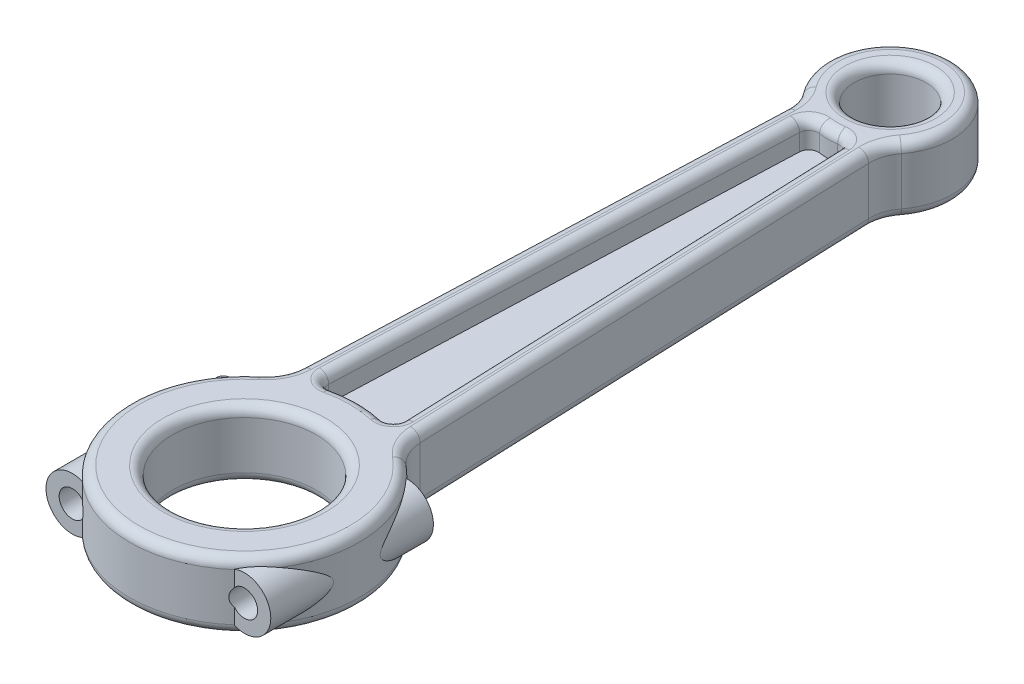
SolidWorks part; units mm, degrees
ref_plane "Alzado" through (0, 0, 0) normal (0, 0, 1) x (1, 0, 0)
ref_plane "Planta" through (0, 0, 0) normal (0, 1, 0) x (1, 0, 0)
ref_plane "Vista lateral" through (0, 0, 0) normal (1, 0, 0) x (0, 0, -1)
sketch "Croquis1" plane through (0, 0, 0) normal (0, 1, 0) x (1, 0, 0)
  line L0 (-12.5, 20.4878) -> (12.5, 20.4878) construction
  line L1 (8.5, 125.1638) -> (-8.5, 125.1638) construction
  line L2 (0, 0) -> (0, 135) construction
  line L3 (-8.6263, 121.8586) -> (-12.3507, 24.3944)
  line L4 (8.6263, 121.8586) -> (12.3507, 24.3944)
  line L5 (-4.1296, 121.6868) -> (-7.854, 24.2226) construction
  line L6 (-4.185, 120.2366) -> (-7.8083, 25.419)
  line L7 (4.185, 120.2366) -> (7.8083, 25.419)
  line L8 (4.1296, 121.6868) -> (7.854, 24.2226) construction
  arc A0 (-15.2587, 18.5249) -> (15.2587, 18.5249) centre (0, 0) ccw
  arc A1 (10.2889, 127.054) -> (-10.2889, 127.054) centre (0, 135) ccw
  arc A2 (-4.185, 120.2366) -> (-1.8949, 122.1388) centre (-2.1865, 120.1602) cw
  arc A3 (15.2587, 18.5249) -> (12.3507, 24.3944) centre (20.3449, 24.6999) cw
  arc A4 (-15.2587, 18.5249) -> (-12.3507, 24.3944) centre (-20.3449, 24.6999) ccw
  arc A5 (10.2889, 127.054) -> (8.6263, 121.8586) centre (16.6205, 122.1641) ccw
  arc A6 (-8.6263, 121.8586) -> (-10.2889, 127.054) centre (-16.6205, 122.1641) ccw
  arc A7 (-1.8949, 122.1388) -> (1.8949, 122.1388) centre (0, 135) ccw
  arc A8 (-15.2587, 18.5249) -> (15.2587, 18.5249) centre (0, 0) ccw
  circle A9 centre (0, 135) radius 7.5
  arc A11 (5.3628, 23.3932) -> (-5.3628, 23.3932) centre (0, 0) ccw
  arc A13 (-4.1296, 121.6868) -> (-6.7273, 129.8045) centre (-16.6205, 122.1641) ccw construction
  arc A15 (6.7273, 129.8045) -> (4.1296, 121.6868) centre (16.6205, 122.1641) ccw construction
  arc A16 (6.7273, 129.8045) -> (-6.7273, 129.8045) centre (0, 135) ccw construction
  arc A17 (10.2889, 127.054) -> (-10.2889, 127.054) centre (0, 135) ccw
  arc A18 (-12.3977, 15.0515) -> (12.3977, 15.0515) centre (0, 0) ccw construction
  arc A19 (-12.3977, 15.0515) -> (-7.854, 24.2226) centre (-20.3449, 24.6999) ccw construction
  arc A20 (12.3977, 15.0515) -> (7.854, 24.2226) centre (20.3449, 24.6999) cw construction
  arc A21 (1.8949, 122.1388) -> (4.185, 120.2366) centre (2.1865, 120.1602) cw
  arc A22 (5.3628, 23.3932) -> (7.8083, 25.419) centre (5.8097, 25.3426) ccw
  arc A23 (-5.3628, 23.3932) -> (-7.8083, 25.419) centre (-5.8097, 25.3426) cw
  dimension "D2" = 24
  dimension "D4" = 13
  dimension "D6" = 8
  dimension "D7" = 2
  dimension "D9" = 15
  dimension "D1" = 25
  dimension "D3" = 17
  dimension "D5" = 135
  dimension "D8" = 4.5
extrude "Saliente-Extruir2" add sketch "Croquis1" along normal mid plane 14 contours A6 L3 A4 A0 A3 L4 A5 A1 A9 A11 A23 L6 A2 A7 A21 L7 A22 region at (-7.3003, 0, -125.1466)
sketch "Croquis2" plane through (0, 0, 0) normal (0, 1, 0) x (1, 0, 0)
  line L0 (-4.185, 120.2366) -> (-7.8083, 25.419) construction
  line L1 (4.185, 120.2366) -> (7.8083, 25.419) construction
  line L2 (-4.185, 120.2366) -> (-7.8083, 25.419)
  line L3 (4.185, 120.2366) -> (7.8083, 25.419)
  arc A0 (-1.8949, 122.1388) -> (-4.185, 120.2366) centre (-2.1865, 120.1602) ccw construction
  arc A1 (-1.8949, 122.1388) -> (1.8949, 122.1388) centre (0, 135) ccw construction
  arc A2 (4.185, 120.2366) -> (1.8949, 122.1388) centre (2.1865, 120.1602) ccw construction
  arc A3 (-7.8083, 25.419) -> (-5.3628, 23.3932) centre (-5.8097, 25.3426) ccw construction
  arc A4 (5.3628, 23.3932) -> (-5.3628, 23.3932) centre (0, 0) ccw construction
  arc A5 (5.3628, 23.3932) -> (7.8083, 25.419) centre (5.8097, 25.3426) ccw construction
  arc A6 (-1.8949, 122.1388) -> (-4.185, 120.2366) centre (-2.1865, 120.1602) ccw
  arc A7 (-1.8949, 122.1388) -> (1.8949, 122.1388) centre (0, 135) ccw
  arc A8 (4.185, 120.2366) -> (1.8949, 122.1388) centre (2.1865, 120.1602) ccw
  arc A9 (-7.8083, 25.419) -> (-5.3628, 23.3932) centre (-5.8097, 25.3426) ccw
  arc A10 (5.3628, 23.3932) -> (-5.3628, 23.3932) centre (0, 0) ccw
  arc A11 (5.3628, 23.3932) -> (7.8083, 25.419) centre (5.8097, 25.3426) ccw
extrude "Saliente-Extruir3" add sketch "Croquis2" along normal mid plane 3
sketch "Croquis3" plane through (0, 0, 0) normal (0, 0, 1) x (1, 0, 0)
  line L0 (-18, 0) -> (18, 0) construction
  circle A0 centre (-18, 0) radius 5.5
  circle A1 centre (18, 0) radius 5.5
  dimension "D2" = 11
  dimension "D1" = 36
extrude "Saliente-Extruir6" add sketch "Croquis3" along normal blind 18 and the other way blind 16 contours A1 | A0
sketch "Croquis6" plane through (0, 0, 0) normal (0, 0, 1) x (1, 0, 0)
  line L0 (-18, 0) -> (18, 0) construction
  circle A0 centre (-18, 0) radius 2.75
  circle A1 centre (18, 0) radius 2.75
  dimension "D2" = 5.5
  dimension "D1" = 36
extrude "Cortar-Extruir4" cut sketch "Croquis6" against normal mid plane 48
sketch "Croquis7" plane through (0, 7, 0) normal (0, 1, 0) x (1, 0, 0)
  circle A0 centre (0, 0) radius 15
  dimension "D1" = 30
extrude "Cortar-Extruir5" cut sketch "Croquis7" against normal up to next
fillet "Redondeo1" radius 2 36 edges at (0, -7, -24) (-7.0856, -7, -23.8024) (-5.9966, -7, -72.8278) (-3.4644, -7, -121.6987) (0, -7, -122) (3.4644, -7, -121.6987) (5.9966, -7, -72.8278) (-10.4885, 7, -73.1265) (-13.1764, 7, -21.1484) (0, 7, 24) (13.1764, 7, -21.1484) (10.4885, 7, -73.1265) (9.0011, 7, -124.6024) (0, 7, -148) (-3.4644, 7, -121.6987) (0, 7, -122) (3.4644, 7, -121.6987) (5.9966, 7, -72.8278) (7.0856, 7, -23.8024) (0, 7, -24) (-7.0856, 7, -23.8024) (0, -7, 15) (7.0856, -7, -23.8024) (-9.0011, 7, -124.6024) (0, 7, -127.5) (-5.9966, 7, -72.8278) (0, 7, 15) (9.0011, -7, -124.6024) (10.4885, -7, -73.1265) (13.1764, -7, -21.1484) (0, -7, 24) (-13.1764, -7, -21.1484) (-10.4885, -7, -73.1265) (-9.0011, -7, -124.6024) (0, -7, -148) (0, -7, -127.5)
